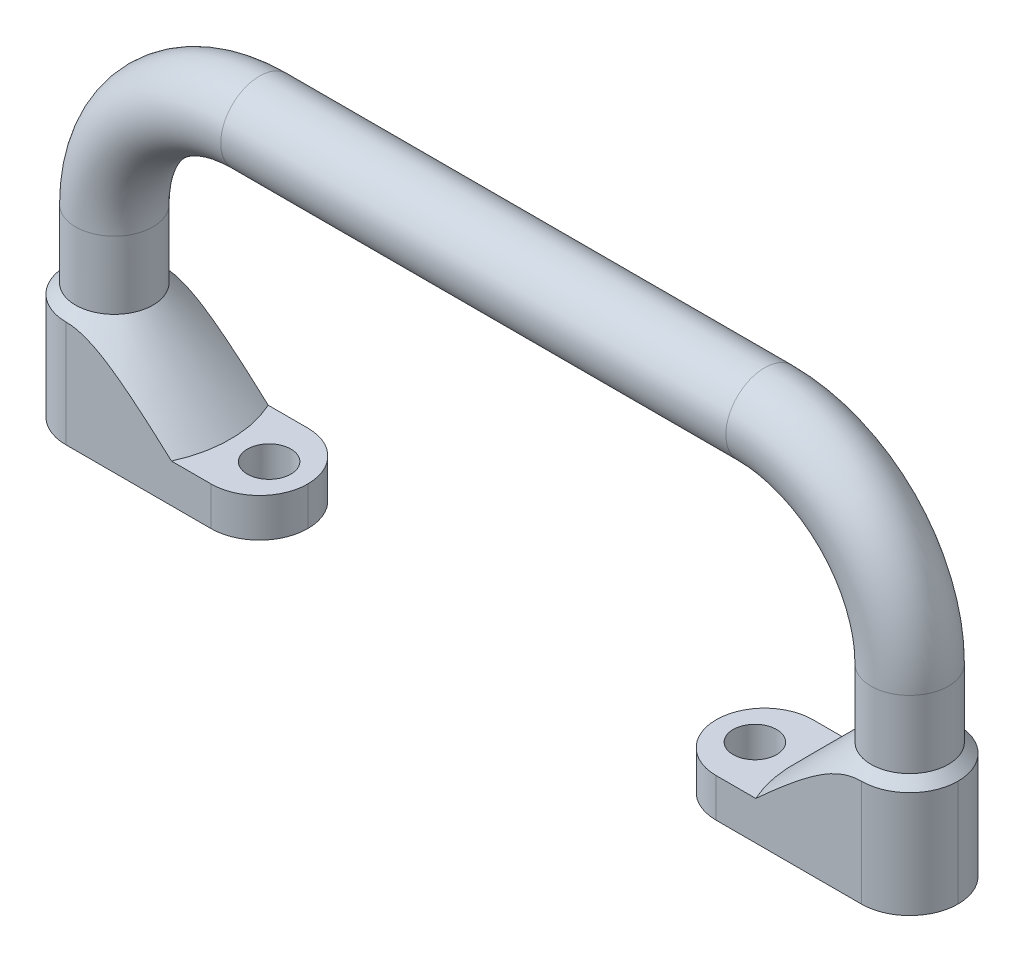
SolidWorks part; units mm, degrees
ref_plane "Piano frontale" through (0, 0, 0) normal (0, 0, 1) x (1, 0, 0)
ref_plane "Piano superiore" through (0, 0, 0) normal (0, 1, 0) x (1, 0, 0)
ref_plane "Piano destro" through (0, 0, 0) normal (1, 0, 0) x (0, 0, -1)
sketch "Schizzo1" plane through (0, 0, 0) normal (0, 0, 1) x (1, 0, 0)
  line L0 (-41.1, 0) -> (-41.1, 15)
  line L1 (-26.1, 30) -> (26.1, 30)
  line L2 (41.1, 15) -> (41.1, 0)
  line L3 (0, 0) -> (0, 30) construction
  line L4 (-41.1, 0) -> (41.1, 0) construction
  arc A0 (26.1, 30) -> (41.1, 15) centre (26.1, 15) cw
  arc A1 (-26.1, 30) -> (-41.1, 15) centre (-26.1, 15) ccw
  point P9 (41.1, 30)
  point P12 (-41.1, 30)
  dimension "D3" = 15
  dimension "D1" = 82.2
  dimension "D2" = 30
sweep "Sweep1" add path "Schizzo1" circular profile diameter 8 parameters "D3"=8
sketch "Schizzo8" plane through (0, 0, 0) normal (0, -1, 0) x (1, 0, 0)
  line L0 (-46.1, 0) -> (46.1, 0) construction
  line L1 (-46.1, 5) -> (-21.1, 5)
  line L2 (-46.1, 5) -> (-46.1, -5)
  line L3 (-46.1, -5) -> (-21.1, -5)
  line L4 (46.1, 5) -> (46.1, -5)
  line L5 (-21.1, 5) -> (-21.1, -5)
  line L6 (21.1, 5) -> (21.1, -5)
  line L7 (21.1, 5) -> (46.1, 5)
  line L8 (21.1, -5) -> (46.1, -5)
  point P6 (0, 0)
  dimension "D1" = 10
  dimension "D2" = 92.2
  dimension "D3" = 25
extrude "Estrusione-Estrusione1" add sketch "Schizzo8" along normal blind 4
fillet "Raccordo1" radius 5 8 edges at (-46.1, -2, -5) (-46.1, -2, 5) (-21.1, -2, -5) (-21.1, -2, 5) (21.1, -2, -5) (21.1, -2, 5) (46.1, -2, -5) (46.1, -2, 5)
chamfer "Smusso1" distance 8 angle 45 2 edges at (-41.1, 0, 4) (41.1, 0, 4)
sketch "Schizzo10" plane through (0, 0, 0) normal (0, 1, 0) x (1, 0, 0)
  line L0 (-29.1, 0) -> (-21.1, 0) construction
  line L2 (21.1, 0) -> (29.1, 0) construction
  arc A0 (-30.1913, -5) -> (-30.1913, 5) centre (-41.1, 0) ccw construction
  arc A1 (-26.1, -5) -> (-21.1, 0) centre (-26.1, 0) ccw construction
  arc A2 (30.1913, 5) -> (30.1913, -5) centre (41.1, 0) ccw construction
  point P0 (-25.1, 0)
  point P2 (25.1, 0)
  point P25 (26.5, 0)
hole_wizard "Foro per Vite M4-1" positions "Schizzo10" profile "Schizzo11" hole size "M4" standard "ISO"
sketch "Schizzo11" plane through (-25.1, 0, 0) normal (1, 0, 0) x (0, 0, 1)
  line L0 (0, 0) -> (0, 14.3519)
  line L1 (0, 14.3519) -> (2.25, 13)
  line L2 (2.25, 13) -> (2.25, 0)
  line L5 (2.25, 0) -> (0, 0)
  line L10 (0, 14.3519) -> (-2.25, 13) construction
  line L11 (0, -6.35) -> (0, 107.95) construction
  dimension "Hole Dia." = 4.5
  dimension "Hole Depth" = 13
  dimension "Drill Angle" = 118
